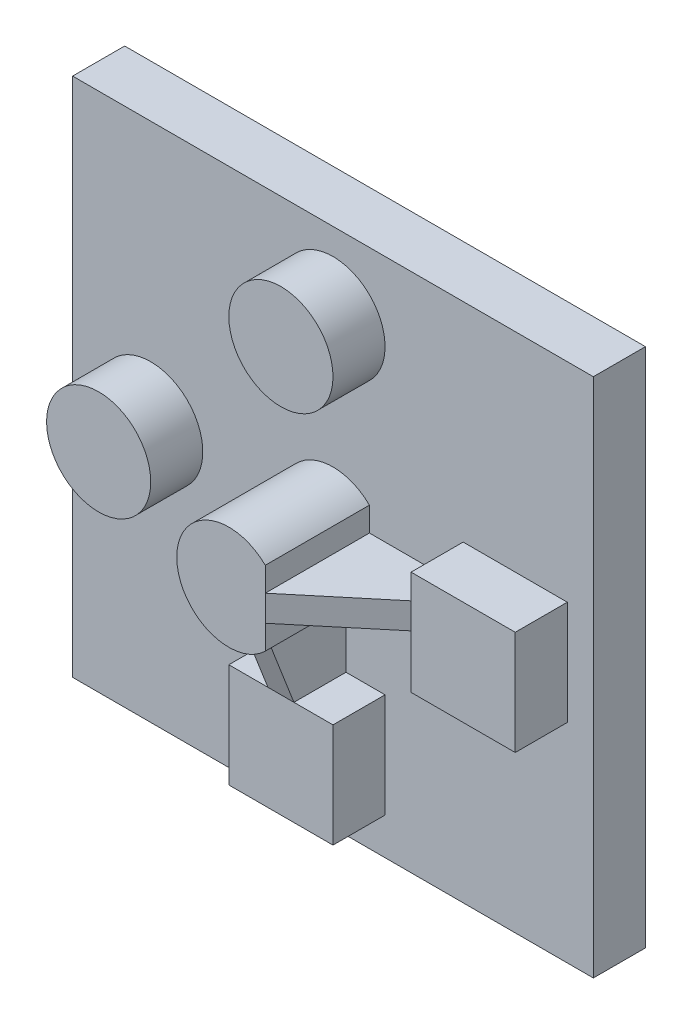
SolidWorks part; units mm, degrees
ref_plane "Piano frontale" through (0, 0, 0) normal (0, 0, 1) x (1, 0, 0)
ref_plane "Piano superiore" through (0, 0, 0) normal (0, 1, 0) x (1, 0, 0)
ref_plane "Piano destro" through (0, 0, 0) normal (1, 0, 0) x (0, 0, -1)
sketch "Schizzo1" plane through (0, 0, 0) normal (0, 0, 1) x (1, 0, 0)
  line L0 (0, 100) -> (100, 100)
  line L1 (100, 100) -> (100, 0)
  line L2 (100, 0) -> (0, 0)
  line L3 (0, 0) -> (0, 100)
  dimension "D1" = 100
  dimension "D2" = 100
extrude "Estrusione-Estrusione1" add sketch "Schizzo1" along normal mid plane 10
sketch "Schizzo2" plane through (0, 0, 5) normal (0, 0, 1) x (1, 0, 0)
  line L0 (0, 100) -> (100, 0) construction
  line L1 (100, 100) -> (0, 0) construction
  line L2 (57, 57.1414) -> (57, 42.8586)
  line L3 (50, 0) -> (50, 100) construction
  line L4 (0, 0) -> (100, 0) construction
  line L5 (100, 100) -> (0, 100) construction
  line L6 (0, 50) -> (100, 50) construction
  line L7 (0, 100) -> (0, 0) construction
  line L8 (100, 0) -> (100, 100) construction
  line L10 (75, 60) -> (95, 60)
  line L11 (75, 60) -> (75, 40)
  line L12 (75, 40) -> (95, 40)
  line L13 (95, 60) -> (95, 40)
  line L14 (75, 60) -> (95, 40) construction
  line L15 (75, 40) -> (95, 60) construction
  line L16 (40, 27.0986) -> (60, 27.0986)
  line L17 (40, 27.0986) -> (40, 7.0986)
  line L18 (40, 7.0986) -> (60, 7.0986)
  line L19 (60, 27.0986) -> (60, 7.0986)
  line L20 (40, 27.0986) -> (60, 7.0986) construction
  line L21 (40, 7.0986) -> (60, 27.0986) construction
  circle A0 centre (50, 50) radius 10
  circle A1 centre (50, 85) radius 10
  circle A2 centre (15, 50) radius 10
  point P28 (85, 50)
  point P33 (50, 17.0986)
  point P38 (0, 0)
  dimension "D1" = 20
  dimension "D11" = 20
  dimension "D12" = 20
  dimension "D2" = 7
  dimension "D3" = 35
  dimension "D4" = 35
  dimension "D5" = 20
  dimension "D6" = 20
  dimension "D7" = 20
  dimension "D8" = 32.9014
  dimension "D9" = 35
  dimension "D10" = 20
extrude "Estrusione-Estrusione2" add sketch "Schizzo2" along normal blind 10 contours A1 | L19 L16 L17 L18 | L13 L10 L11 L12 | A2 region at (85, 50, 5) region at (50, 17.0986, 5) region at (50, 85, 5) region at (15, 50, 5)
extrude "Estrusione-Estrusione3" add sketch "Schizzo2<3>" along normal blind 20 contours L2 A0 region at (49.1469, 50, 5)
sketch "Schizzo2<3>" plane through (0, 0, 5) normal (0, 0, 1) x (1, 0, 0) same geometry as "Schizzo2"
sketch "Schizzo16" plane through (0, 0, 25) normal (0, 0, 1) x (1, 0, 0)
  line L0 (50, 50) -> (109.2624, 50) construction
  line L1 (50, 50) -> (50, 108.6401) construction
  line L2 (50, 50) -> (-19.1993, 50) construction
  line L3 (50, 50) -> (50, -11.0162) construction
ref_plane "Piano1" through (0, 50, 0) normal (0, -1, 0) x (1, 0, 0)
sketch "Schizzo17" plane through (0, 50, 0) normal (0, -1, 0) x (1, 0, 0)
  line L0 (75, 10) -> (57, 25)
  line L1 (75, 15) -> (75, 5) construction
ref_plane "Piano3" through (50, 0, 0) normal (-1, 0, 0) x (0, -1, 0)
sketch "Schizzo19" plane through (50, 0, 0) normal (-1, 0, 0) x (0, -1, 0)
  line L0 (-27.0986, 15) -> (-40, 20)
  line L1 (-40, 5) -> (-40, 25) construction
  line L2 (-40, 5) -> (-60, 5) construction
  point P5 (0, 0)
  dimension "D1" = 15
ref_plane "Piano4" through (50, 0, 0) normal (1, 0, 0) x (0, 1, 0)
sketch "Schizzo20" plane through (50, 0, 0) normal (1, 0, 0) x (0, 1, 0)
  line L0 (60, 25) -> (75, 15)
ref_plane "Piano5" through (0, 50, 0) normal (0, 1, 0) x (-1, 0, 0)
sketch "Schizzo21" plane through (0, 50, 0) normal (0, 1, 0) x (-1, 0, 0)
  line L0 (-40, 25) -> (-25, 10)
  line L1 (-25, 15) -> (-25, 5) construction
rib "Nervatura6" sketch "Schizzo17" sketch "Schizzo17" thickness 5 extrusion direction parallel to sketch draft on no parameters "D1"=5
rib "Nervatura7" sketch "Schizzo19" sketch "Schizzo19" thickness 5 extrusion direction parallel to sketch draft on no parameters "D1"=5
